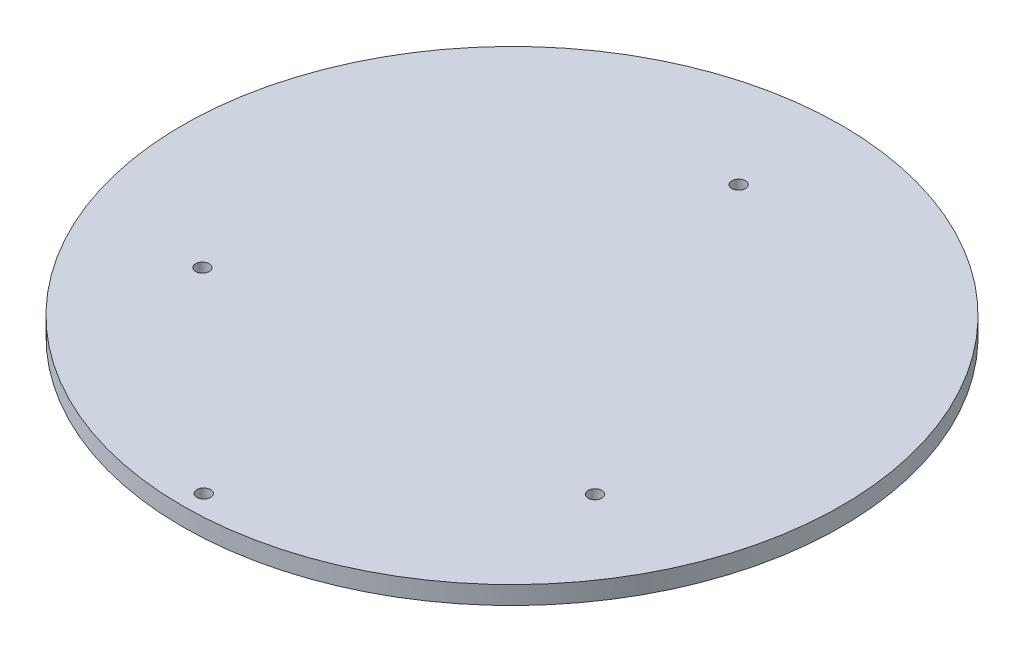
SolidWorks part; units mm, degrees
ref_plane "Ebene vorne" through (0, 0, 0) normal (0, 0, 1) x (1, 0, 0)
ref_plane "Ebene oben" through (0, 0, 0) normal (0, 1, 0) x (1, 0, 0)
ref_plane "Ebene rechts" through (0, 0, 0) normal (1, 0, 0) x (0, 0, -1)
sketch "Sketch1" plane through (0, 0, 0) normal (0, 1, 0) x (1, 0, 0)
  circle A0 centre (0, 0) radius 72.7
  dimension "D1" = 145.4
extrude "Boss-Extrude1" add sketch "Sketch1" along normal blind 4
sketch "Sketch2" plane through (0, 4, 0) normal (0, 1, 0) x (1, 0, 0)
  line L0 (0, 0) -> (0, 66.4755) construction
  circle A0 centre (0, 50) radius 1.5
  dimension "D1" = 3
  dimension "D2" = 50
extrude "Cut-Extrude1" cut sketch "Sketch2" against normal through all
ref_axis "Axis1" through (0, 33.6, 0) along (0, -1, 0)
pattern_circular "CirPattern1" count 3 over 360 about axis through (0, 33.6, 0) along (0, -1, 0) of "Cut-Extrude1"
sketch "Sketch3" plane through (0, 4, 0) normal (0, 1, 0) x (1, 0, 0)
  circle A0 centre (0, -68) radius 1.5
  dimension "D1" = 3
  dimension "D2" = 68
extrude "Cut-Extrude2" cut sketch "Sketch3" against normal through all
